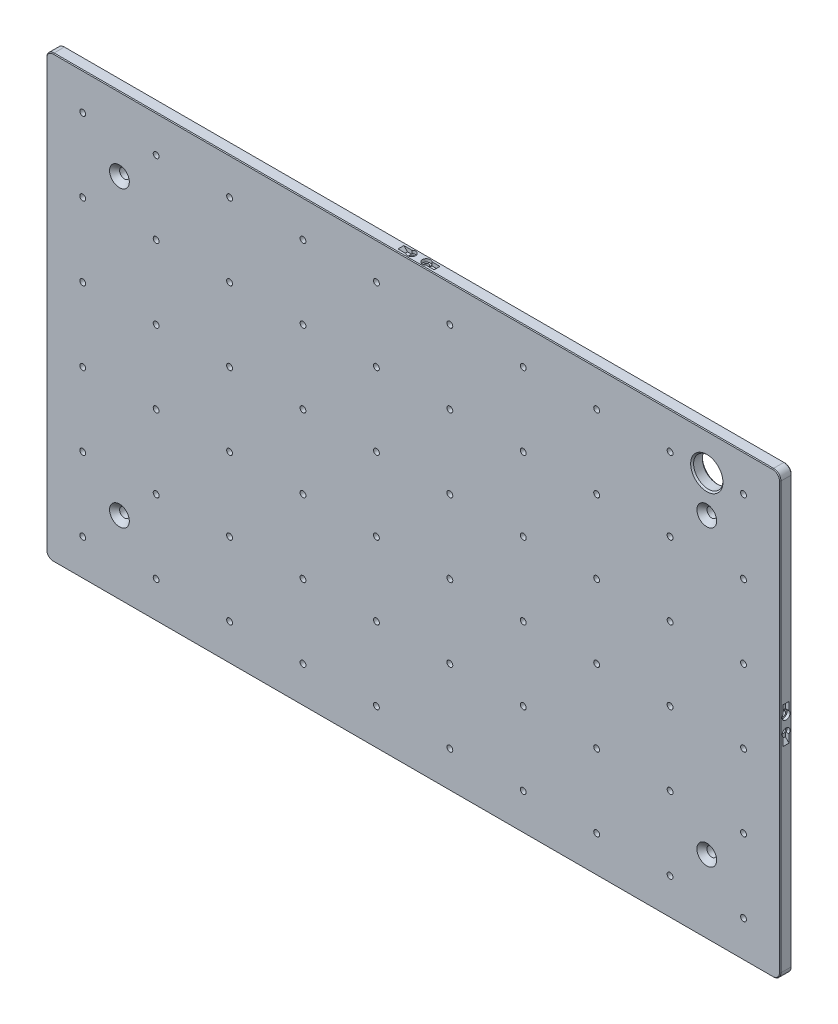
SolidWorks part; units mm, degrees
ref_plane "前视基准面" through (0, 0, 0) normal (0, 0, 1) x (1, 0, 0)
ref_plane "上视基准面" through (0, 0, 0) normal (0, 1, 0) x (1, 0, 0)
ref_plane "右视基准面" through (0, 0, 0) normal (1, 0, 0) x (0, 0, -1)
other "Configuration Table"
sketch "草图1" plane through (0, 0, 0) normal (0, 0, 1) x (1, 0, 0)
  line L1 (-250, -150) -> (250, -150)
  line L2 (-250, -150) -> (-250, 150)
  line L3 (-250, 150) -> (250, 150)
  line L4 (250, -150) -> (250, 150)
  line L5 (-250, -150) -> (250, 150) construction
  line L6 (-250, 150) -> (250, -150) construction
  point P0 (0, 0)
  dimension "D1" = 500
  dimension "D2" = 300
extrude "凸台-拉伸1" add sketch "草图1" along normal blind 8
hole_wizard "孔1" positions "草图2" profile "草图3" legacy end condition through all
sketch "草图2" plane through (0, 0, 8) normal (0, 0, 1) x (1, 0, 0)
  line L0 (-250, 150) -> (-250, -150) construction
  line L2 (-250, -150) -> (250, -150) construction
  point P0 (-225, -125)
  dimension "D1" = 25
  dimension "D2" = 25
sketch "草图3" plane through (-225, -125, 8) normal (1, 0, 0) x (0, -1, 0)
  line L0 (0, 0) -> (0, 8)
  line L1 (0, 8) -> (2, 8)
  line L2 (2, 8) -> (2, 0)
  line L3 (2, 0) -> (0, 0)
  line L4 (0, 110) -> (0, -10) construction
  dimension "直径" = 4
  dimension "深度" = 8
pattern_linear "阵列(线性)1" count 10 spacing 50 along (1, 0, 0) count 6 spacing 50 along (0, 1, 0) of "孔1"
hole_wizard "孔2" positions "草图4" profile "草图5" legacy end condition through all
sketch "草图4" plane through (0, 0, 8) normal (0, 0, 1) x (1, 0, 0)
  line L0 (-250, 0) -> (250, 0) construction
  line L1 (-250, 150) -> (-250, -150) construction
  line L2 (250, -150) -> (250, 150) construction
  line L4 (0, -150) -> (0, 150) construction
  line L5 (-250, -150) -> (250, -150) construction
  line L6 (250, 150) -> (-250, 150) construction
  point P0 (-200, 100)
  dimension "D1" = 100
  dimension "D2" = 200
sketch "草图5" plane through (-200, 100, 8) normal (1, 0, 0) x (0, -1, 0)
  line L0 (0, 0) -> (0, 8)
  line L1 (0, 8) -> (3.3, 8)
  line L2 (3.3, 8) -> (3.3, 3.42)
  line L3 (3.3, 3.42) -> (6.72, 0)
  line L4 (6.72, 0) -> (0, 0)
  line L5 (0, -6.4453) -> (0, 115.525) construction
  line L6 (-3.3, 3.42) -> (-6.72, 0) construction
  dimension "直径" = 6.6
  dimension "深度" = 8
  dimension "锥坑角度" = 90
  dimension "锥坑直径" = 13.44
pattern_linear "阵列(线性)2" count 2 spacing 400 along (1, 0, 0) count 2 spacing 200 along (0, -1, 0) of "孔2"
hole_wizard "孔3" positions "草图6" profile "草图7" legacy end condition through all
sketch "草图6" plane through (0, 0, 8) normal (0, 0, 1) x (1, 0, 0)
  line L0 (175, 125) -> (225, 125) construction
  line L1 (200, 100) -> (200, 125) construction
  point P0 (200, 125)
sketch "草图7" plane through (200, 125, 8) normal (1, 0, 0) x (0, -1, 0)
  line L0 (0, 0) -> (0, 8)
  line L1 (0, 8) -> (10, 8)
  line L2 (10, 8) -> (10, 0)
  line L3 (10, 0) -> (0, 0)
  line L4 (0, 110) -> (0, -10) construction
  dimension "直径" = 20
  dimension "深度" = 8
chamfer "倒角1" distance 1 angle 45 2 edges at (210, 125, 0) (210, 125, 8)
ref_plane "基准面1" through (0, 0, 0) normal (1, 0, 0) x (0, 0, -1)
split "分割1" trim tools "基准面1" bodies to split 111 resulting bodies 112 113
ref_plane "基准面2" through (0, 0, 0) normal (0, 1, 0) x (1, 0, 0)
split "分割2" trim tools "基准面2" bodies to split 112 resulting bodies 114 115
split "分割3" trim tools "基准面2" bodies to split 113 resulting bodies 116 117
hole_wizard "孔4" positions "草图9" profile "草图10" legacy
sketch "草图9" plane through (0, 150, 0) normal (0, 1, 0) x (1, 0, 0)
  line L0 (0, -62.4802) -> (0, 62.4802) construction
  line L2 (0, 0) -> (-250, 0) construction
  point P0 (-5, -4)
  dimension "D1" = 5
  dimension "D2" = 4
sketch "草图10" plane through (-5, 150, 4) normal (1, 0, 0) x (0, 0, 1)
  line L0 (0, 0) -> (0, 15)
  line L1 (0, 15) -> (1.6, 15)
  line L2 (1.6, 15) -> (1.6, 0)
  line L3 (1.6, 0) -> (0, 0)
  line L4 (0, 110) -> (0, -10) construction
  dimension "直径" = 3.2
  dimension "深度" = 15
sketch "草图11" plane through (0, 0, 0) normal (1, 0, 0) x (0, 0, -1)
  line L0 (0, 150) -> (-8, 150) construction
  line L1 (-7.25, 139.75) -> (-0.75, 139.75)
  line L2 (-7.25, 139.75) -> (-7.25, 146.25)
  line L3 (-7.25, 146.25) -> (-0.75, 146.25)
  line L4 (-0.75, 139.75) -> (-0.75, 146.25)
  line L5 (-7.25, 139.75) -> (-0.75, 146.25) construction
  line L6 (-7.25, 146.25) -> (-0.75, 139.75) construction
  line L8 (-4, 150) -> (-4, 136.8104) construction
  point P0 (-4, 143)
  dimension "D1" = 6.5
  dimension "D2" = 6.5
  dimension "D3" = 7
extrude "切除-拉伸1" cut sketch "草图11" against normal blind 12
ref_plane "基准面3" through (-125, 0, 0) normal (1, 0, 0) x (0, 0, -1)
ref_plane "基准面4" through (0, 75, 0) normal (0, -1, 0) x (-1, 0, 0)
combine bodies "组合1" operation type add bodies to combine 119 114
mirror "镜向1" about plane through (0, 0, 0) normal (1, 0, 0) of "孔4", "切除-拉伸1"
hole_wizard "孔5" positions "草图12" profile "草图13" legacy
sketch "草图12" plane through (0, 150, 0) normal (0, 1, 0) x (1, 0, 0)
  point P14 (-5, -4)
sketch "草图13" plane through (-5, 150, 4) normal (1, 0, 0) x (0, 0, 1)
  line L0 (0, 0) -> (0, 2)
  line L1 (0, 2) -> (2.7, 2)
  line L2 (2.7, 2) -> (2.7, 0)
  line L3 (2.7, 0) -> (0, 0)
  line L4 (0, 110) -> (0, -10) construction
  dimension "直径" = 5.4
  dimension "深度" = 2
sketch "草图15" plane through (0, 150, 0) normal (0, 1, 0) x (1, 0, 0)
  line L0 (-2.3, -4) -> (-10.3435, -4) construction
  line L2 (-9.8138, -6) -> (-6.8138, -6)
  line L3 (-9.8138, -6) -> (-9.8138, -2)
  line L4 (-9.8138, -2) -> (-6.8138, -2)
  line L5 (-6.8138, -6) -> (-6.8138, -2)
  line L6 (-9.8138, -6) -> (-6.8138, -2) construction
  line L7 (-9.8138, -2) -> (-6.8138, -6) construction
  circle A0 centre (-5, -4) radius 2.7 construction
  circle A1 centre (-5, -4) radius 2.7 construction
  point P7 (-8.3138, -4)
  dimension "D1" = 4
  dimension "D2" = 3
extrude "切除-拉伸3" cut sketch "草图15" against normal blind 2.5
chamfer "倒角3" distance 2.5 angle 45 1 edges at (-9.8138, 150, 4)
mirror "镜向14" about plane through (0, 0, 0) normal (1, 0, 0) of "倒角3", "切除-拉伸3", "孔5"
combine bodies "组合4" operation type add bodies to combine 117 115 136
hole_wizard "孔6" positions "草图17" profile "草图18" legacy
sketch "草图17" plane through (0, -150, 0) normal (0, -1, 0) x (-1, 0, 0)
  point P0 (-5, -4)
  point P2 (5, -4)
sketch "草图18" plane through (5, -150, 4) normal (1, 0, 0) x (0, 0, -1)
  line L0 (0, 0) -> (0, 2)
  line L1 (0, 2) -> (2.7, 2)
  line L2 (2.7, 2) -> (2.7, 0)
  line L3 (2.7, 0) -> (0, 0)
  line L4 (0, 110) -> (0, -10) construction
  dimension "直径" = 5.4
  dimension "深度" = 2
hole_wizard "孔7" positions "草图19" profile "草图20" legacy
sketch "草图19" plane through (0, -150, 0) normal (0, -1, 0) x (-1, 0, 0)
  point P0 (5, -4)
  point P2 (-5, -4)
sketch "草图20" plane through (-5, -150, 4) normal (1, 0, 0) x (0, 0, -1)
  line L0 (0, 0) -> (0, 15)
  line L1 (0, 15) -> (1.6, 15)
  line L2 (1.6, 15) -> (1.6, 0)
  line L3 (1.6, 0) -> (0, 0)
  line L4 (0, 110) -> (0, -10) construction
  dimension "直径" = 3.2
  dimension "深度" = 15
sketch "草图21" plane through (0, -150, 0) normal (0, -1, 0) x (1, 0, 0)
  line L0 (-5, 4) -> (-9.5372, 4) construction
  line L1 (5, 4) -> (9.1213, 4) construction
  line L2 (-9.8138, 2) -> (-6.8138, 2)
  line L3 (-9.8138, 2) -> (-9.8138, 6)
  line L4 (-9.8138, 6) -> (-6.8138, 6)
  line L5 (-6.8138, 2) -> (-6.8138, 6)
  line L6 (-9.8138, 2) -> (-6.8138, 6) construction
  line L7 (-9.8138, 6) -> (-6.8138, 2) construction
  line L9 (9.8138, 2) -> (6.8138, 2)
  line L10 (9.8138, 2) -> (9.8138, 6)
  line L11 (9.8138, 6) -> (6.8138, 6)
  line L12 (6.8138, 2) -> (6.8138, 6)
  line L13 (9.8138, 2) -> (6.8138, 6) construction
  line L14 (9.8138, 6) -> (6.8138, 2) construction
  circle A0 centre (-5, 4) radius 2.7 construction
  circle A1 centre (5, 4) radius 2.7 construction
  point P3 (-8.3138, 4)
  point P13 (8.3138, 4)
  dimension "D1" = 3
  dimension "D2" = 4
  dimension "D3" = 3
  dimension "D4" = 4
extrude "切除-拉伸4" cut sketch "草图21" against normal blind 2.5
chamfer "倒角4" distance 2.5 angle 45 2 edges at (9.8138, -150, 4) (-9.8138, -150, 4)
sketch "草图22" plane through (0, 0, 0) normal (1, 0, 0) x (0, 0, -1)
  line L0 (-4, -150) -> (-4, -131.7354) construction
  line L1 (-8, -150) -> (0, -150) construction
  line L3 (-7.25, -139.75) -> (-0.75, -139.75)
  line L4 (-7.25, -139.75) -> (-7.25, -146.25)
  line L5 (-7.25, -146.25) -> (-0.75, -146.25)
  line L6 (-0.75, -139.75) -> (-0.75, -146.25)
  line L7 (-7.25, -139.75) -> (-0.75, -146.25) construction
  line L8 (-7.25, -146.25) -> (-0.75, -139.75) construction
  point P4 (-4, -143)
  dimension "D1" = 7
  dimension "D2" = 6.5
  dimension "D3" = 6.5
extrude "切除-拉伸5" cut sketch "草图22" against normal mid plane 24
sketch "草图24" plane through (-250, 0, 0) normal (-1, 0, 0) x (0, 0, 1)
  line L0 (0, 5.2771) -> (8, 5.2771) construction
  line L1 (0, 150) -> (0, -150) construction
  line L2 (8, 150) -> (8, -150) construction
  line L3 (4, 5.2771) -> (4, -4.7687) construction
  line L4 (3.85, 0) -> (-3.85, 0) construction
  circle A0 centre (4, 5) radius 1.6
  circle A1 centre (4, -5) radius 1.6
  dimension "D3" = 3.2
  dimension "D4" = 3.2
  dimension "D1" = 5
  dimension "D2" = 5
extrude "切除-拉伸6" cut sketch "草图24" against normal blind 15
hole_wizard "孔8" positions "草图25" profile "草图26" legacy
sketch "草图25" plane through (-250, 0, 0) normal (-1, 0, 0) x (0, 0, 1)
  point P0 (4, 5)
  point P3 (4, -5)
sketch "草图26" plane through (-250, 5, 4) normal (0, 1, 0) x (0, 0, 1)
  line L0 (0, 0) -> (0, 2)
  line L1 (0, 2) -> (2.7, 2)
  line L2 (2.7, 2) -> (2.7, 0)
  line L3 (2.7, 0) -> (0, 0)
  line L4 (0, 110) -> (0, -10) construction
  dimension "直径" = 5.4
  dimension "深度" = 2
sketch "草图27" plane through (-250, 0, 0) normal (-1, 0, 0) x (0, 0, 1)
  line L0 (4, 6.9192) -> (4, 15.3399) construction
  line L6 (2, -9.8138) -> (6, -9.8138)
  line L7 (2, -9.8138) -> (2, -6.8138)
  line L8 (2, 9.8138) -> (6, 9.8138)
  line L9 (2, 9.8138) -> (2, 6.8138)
  line L10 (2, 6.8138) -> (6, 6.8138)
  line L11 (6, 9.8138) -> (6, 6.8138)
  line L12 (2, 9.8138) -> (6, 6.8138) construction
  line L13 (2, 6.8138) -> (6, 9.8138) construction
  line L14 (2, -6.8138) -> (6, -6.8138)
  line L15 (6, -9.8138) -> (6, -6.8138)
  line L16 (2, -9.8138) -> (6, -6.8138) construction
  line L17 (2, -6.8138) -> (6, -9.8138) construction
  circle A0 centre (4, 5) radius 2.7 construction
  circle A1 centre (4, -5) radius 2.7 construction
  point P1 (4, -8.3138)
  point P9 (4, 8.3138)
  dimension "D1" = 4
  dimension "D2" = 3
  dimension "D3" = 4
extrude "切除-拉伸7" cut sketch "草图27" against normal blind 2.5
chamfer "倒角5" distance 2.5 angle 45 2 edges at (-250, -9.8138, 4) (-250, 9.8138, 4)
sketch "草图28" plane through (0, 0, 0) normal (0, 1, 0) x (1, 0, 0)
  line L0 (-250, -4) -> (-232.4695, -4) construction
  line L1 (-250, -8) -> (-250, 0) construction
  line L3 (-246.25, -7.25) -> (-239.75, -7.25)
  line L4 (-246.25, -7.25) -> (-246.25, -0.75)
  line L5 (-246.25, -0.75) -> (-239.75, -0.75)
  line L6 (-239.75, -7.25) -> (-239.75, -0.75)
  line L7 (-246.25, -7.25) -> (-239.75, -0.75) construction
  line L8 (-246.25, -0.75) -> (-239.75, -7.25) construction
  point P4 (-243, -4)
  dimension "D1" = 7
  dimension "D2" = 6.5
  dimension "D3" = 6.5
extrude "切除-拉伸9" cut sketch "草图28" against normal mid plane 24
hole_wizard "孔9" positions "草图30" profile "草图31" legacy
sketch "草图30" plane through (250, 0, 0) normal (1, 0, 0) x (0, 0, -1)
  line L5 (-8, 15.95) -> (0, 15.95) construction
  line L6 (-8, -150) -> (-8, 150) construction
  line L7 (0, -150) -> (0, 150) construction
  line L9 (-4, 15.95) -> (-4, -6.4396) construction
  line L11 (3.85, 0) -> (-3.85, 0) construction
  point P0 (-4, 5)
  point P2 (-4, -5)
  dimension "D1" = 5
  dimension "D2" = 5
sketch "草图31" plane through (250, 5, 4) normal (0, 1, 0) x (0, 0, -1)
  line L0 (0, 0) -> (0, 2)
  line L1 (0, 2) -> (2.7, 2)
  line L2 (2.7, 2) -> (2.7, 0)
  line L3 (2.7, 0) -> (0, 0)
  line L4 (0, 110) -> (0, -10) construction
  dimension "直径" = 5.4
  dimension "深度" = 2
hole_wizard "孔10" positions "草图32" profile "草图33" legacy
sketch "草图32" plane through (250, 0, 0) normal (1, 0, 0) x (0, 0, -1)
  point P0 (-4, 5)
  point P3 (-4, -5)
sketch "草图33" plane through (250, 5, 4) normal (0, 1, 0) x (0, 0, -1)
  line L0 (0, 0) -> (0, 15)
  line L1 (0, 15) -> (1.6, 15)
  line L2 (1.6, 15) -> (1.6, 0)
  line L3 (1.6, 0) -> (0, 0)
  line L4 (0, 110) -> (0, -10) construction
  dimension "直径" = 3.2
  dimension "深度" = 15
sketch "草图34" plane through (250, 0, 0) normal (1, 0, 0) x (0, 0, -1)
  line L0 (-4, 1.2266) -> (-4, -8.7734) construction
  line L2 (-6, 9.8138) -> (-2, 9.8138)
  line L3 (-6, 9.8138) -> (-6, 6.8138)
  line L4 (-6, 6.8138) -> (-2, 6.8138)
  line L5 (-2, 9.8138) -> (-2, 6.8138)
  line L6 (-6, 9.8138) -> (-2, 6.8138) construction
  line L7 (-6, 6.8138) -> (-2, 9.8138) construction
  line L8 (-6, -9.8138) -> (-2, -9.8138)
  line L9 (-6, -9.8138) -> (-6, -6.8138)
  line L10 (-6, -6.8138) -> (-2, -6.8138)
  line L11 (-2, -9.8138) -> (-2, -6.8138)
  line L12 (-6, -9.8138) -> (-2, -6.8138) construction
  line L13 (-6, -6.8138) -> (-2, -9.8138) construction
  circle A0 centre (-4, 5) radius 2.7 construction
  circle A1 centre (-4, 5) radius 2.7 construction
  circle A2 centre (-4, -5) radius 2.7 construction
  point P1 (-4, 8.3138)
  point P2 (-4, -8.3138)
  dimension "D1" = 4
  dimension "D2" = 3
  dimension "D3" = 4
  dimension "D4" = 3
extrude "切除-拉伸10" cut sketch "草图34" against normal blind 2.5
chamfer "倒角6" distance 2.5 angle 45 2 edges at (250, -9.8138, 4) (250, 9.8138, 4)
sketch "草图36" plane through (0, 0, 0) normal (0, 1, 0) x (1, 0, 0)
  line L0 (243, 0) -> (243, -8) construction
  line L1 (-250, 0) -> (250, 0) construction
  line L2 (-250, -8) -> (250, -8) construction
  line L3 (250, -8) -> (250, 0) construction
  line L4 (246.25, -7.25) -> (239.75, -7.25)
  line L5 (246.25, -7.25) -> (246.25, -0.75)
  line L6 (246.25, -0.75) -> (239.75, -0.75)
  line L7 (239.75, -7.25) -> (239.75, -0.75)
  line L8 (246.25, -7.25) -> (239.75, -0.75) construction
  line L9 (246.25, -0.75) -> (239.75, -7.25) construction
  point P6 (243, -4)
  dimension "D1" = 6.5
  dimension "D2" = 6.5
  dimension "D3" = 7
extrude "切除-拉伸11" cut sketch "草图36" against normal mid plane 24
fillet "圆角2" radius 5 4 edges at (-250, 150, 4) (-250, -150, 4) (250, -150, 4) (250, 150, 4)
chamfer "倒角7" distance 0.5 angle 45 16 edges at (0, 150, 0) (-248.5355, 148.5355, 0) (248.5355, 148.5355, 0) (-250, 0, 0) (250, 0, 0) (-248.5355, -148.5355, 0) (248.5355, -148.5355, 0) (0, -150, 0) (0, 150, 8) (-248.5355, 148.5355, 8) (248.5355, 148.5355, 8) (-250, 0, 8) (250, 0, 8) (-248.5355, -148.5355, 8) (248.5355, -148.5355, 8) (0, -150, 8)
ref_plane "基准面5" through (-62.5, 0, 0) normal (1, 0, 0) x (0, 0, -1)
ref_plane "基准面6" through (125, 0, 0) normal (1, 0, 0) x (0, 0, -1)
ref_plane "基准面10" through (100, 0, 0) normal (1, 0, 0) x (0, 0, -1)
ref_plane "基准面11" through (-90, 0, 0) normal (-1, 0, 0) x (0, 0, 1)
